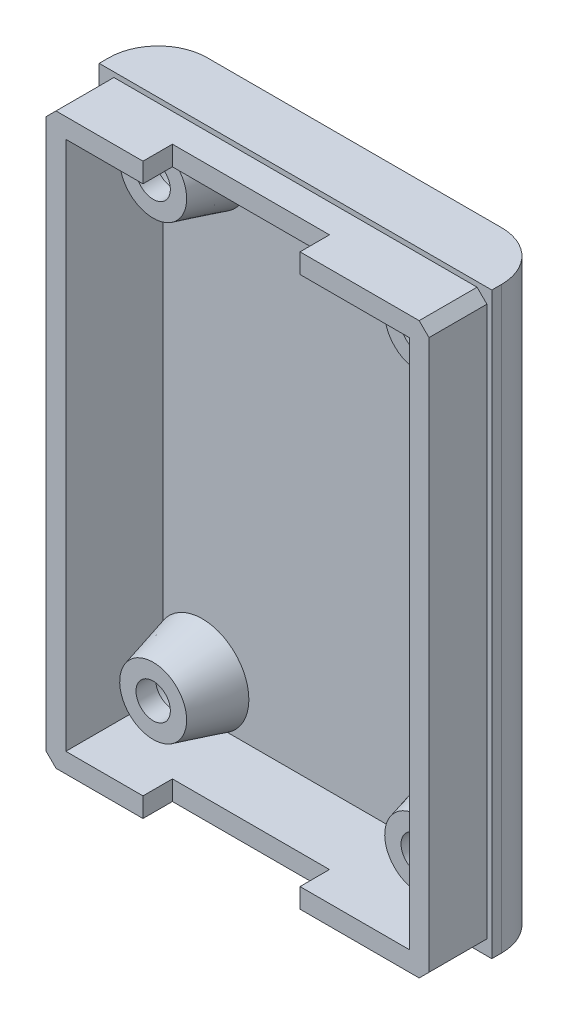
SolidWorks part; units mm, degrees
ref_plane "Спереди" through (0, 0, 0) normal (0, 0, 1) x (1, 0, 0)
ref_plane "Сверху" through (0, 0, 0) normal (0, 1, 0) x (1, 0, 0)
ref_plane "Справа" through (0, 0, 0) normal (1, 0, 0) x (0, 0, -1)
sketch "outline" plane through (0, 0, 0) normal (0, 0, 1) x (1, 0, 0)
  line L0 (-20.5405, -29.5) -> (19.4595, -29.5)
  line L1 (19.4595, -29.5) -> (19.4595, 29.5)
  line L2 (19.4595, 29.5) -> (-20.5405, 29.5)
  line L3 (-20.5405, 29.5) -> (-20.5405, -29.5)
  circle A0 centre (-14.0405, -23) radius 3.25
  circle A1 centre (12.9595, -23) radius 3.25
  circle A2 centre (12.9595, 23) radius 3.25
  circle A3 centre (-14.0405, 23) radius 3.25
  dimension "D1" = 6.5
sketch "base" plane through (0, 0, 0) normal (0, 0, 1) x (1, 0, 0)
  line L0 (-20.5405, -29.5) -> (19.4595, -29.5)
  line L1 (19.4595, -29.5) -> (19.4595, 29.5)
  line L2 (19.4595, 29.5) -> (-20.5405, 29.5)
  line L3 (-20.5405, 29.5) -> (-20.5405, -29.5)
extrude "Бобышка-Вытянуть1" add sketch "base" along normal blind 2
sketch "Эскиз2" plane through (0, 0, 2) normal (0, 0, 1) x (1, 0, 0)
  line L0 (-20.5405, -29.5) -> (19.4595, -29.5) construction
  line L1 (-18.0405, 27) -> (16.9595, 27)
  line L2 (-18.0405, 27) -> (-18.0405, -27)
  line L3 (-18.0405, -27) -> (16.9595, -27)
  line L4 (16.9595, 27) -> (16.9595, -27)
  line L5 (19.4595, -29.5) -> (19.4595, 29.5) construction
  line L6 (19.4595, 29.5) -> (-20.5405, 29.5) construction
  line L7 (-20.5405, 29.5) -> (-20.5405, -29.5) construction
  line L8 (-20.5405, -29.5) -> (19.4595, -29.5)
  line L9 (19.4595, -29.5) -> (19.4595, 29.5)
  line L10 (19.4595, 29.5) -> (-20.5405, 29.5)
  line L11 (-20.5405, 29.5) -> (-20.5405, -29.5)
  dimension "D1" = 2.5
  dimension "D2" = 2.5
  dimension "D3" = 2.5
  dimension "D4" = 2.5
extrude "Бобышка-Вытянуть2" add sketch "Эскиз2" along normal blind 10
sketch "Эскиз3" plane through (0, 0, 2) normal (0, 0, 1) x (1, 0, 0)
  circle A0 centre (-14.0405, -23) radius 3.25 construction
  circle A1 centre (12.9595, -23) radius 3.25 construction
  circle A2 centre (12.9595, 23) radius 3.25 construction
  circle A3 centre (-14.0405, 23) radius 3.25 construction
  circle A4 centre (-14.0405, -23) radius 3.25
  circle A5 centre (12.9595, -23) radius 3.25
  circle A6 centre (12.9595, 23) radius 3.25
  circle A7 centre (-14.0405, 23) radius 3.25
extrude "Бобышка-Вытянуть3" add sketch "Эскиз3" along normal blind 5
sketch "Эскиз4" plane through (0, 0, 0) normal (0, 0, -1) x (-1, 0, 0)
  circle A0 centre (-12.9595, -23) radius 3.25
  circle A1 centre (14.0405, -23) radius 3.25
  circle A2 centre (14.0405, 23) radius 3.25
  circle A3 centre (-12.9595, 23) radius 3.25
  circle A4 centre (-12.9595, -23) radius 2.9
  circle A5 centre (14.0405, -23) radius 2.9
  circle A6 centre (14.0405, 23) radius 2.9
  circle A7 centre (-12.9595, 23) radius 2.9
  dimension "D1" = 5.8
  dimension "D2" = 5.8
  dimension "D3" = 5.8
  dimension "D4" = 5.8
extrude "Вырез-Вытянуть2" cut sketch "Эскиз4" against normal blind 5 contours A5 | A4 | A7 | A6 region at (12.9595, -23, 0) region at (-14.0405, -23, 0) region at (-14.0405, 23, 0) region at (12.9595, 23, 0)
chamfer "Фаска1" distance 1.5 angle 75 4 edges at (-10.7905, 23, 2) (16.2095, 23, 2) (-10.7905, -23, 2) (16.2095, -23, 2) first distance on face at (-10.7905, 23, 2)
sketch "Эскиз6" plane through (0, 0, 0) normal (0, 0, -1) x (-1, 0, 0)
  circle A0 centre (-12.9595, 23) radius 1.75
  circle A1 centre (14.0405, 23) radius 1.75
  circle A2 centre (14.0405, -23) radius 1.75
  circle A3 centre (-12.9595, -23) radius 1.75
  dimension "D1" = 3.5
  dimension "D2" = 3.5
  dimension "D3" = 3.5
  dimension "D4" = 3.5
extrude "Вырез-Вытянуть3" cut sketch "Эскиз6" against normal through all
fillet "Скругление1" radius 5 2 edges at (-20.5405, 0, 0) (19.4595, 0, 0)
sketch "Эскиз7" plane through (0, 0, 12) normal (0, 0, 1) x (1, 0, 0)
  line L0 (-20.5405, -29.5) -> (19.4595, -29.5) construction
  line L1 (18.9595, 29) -> (-20.0405, 29)
  line L2 (18.9595, 29) -> (18.9595, -29)
  line L3 (18.9595, -29) -> (-20.0405, -29)
  line L4 (-20.0405, 29) -> (-20.0405, -29)
  line L5 (19.4595, -29.5) -> (19.4595, 29.5) construction
  line L6 (-20.5405, -29.5) -> (19.4595, -29.5) construction
  line L7 (19.4595, 29.5) -> (-20.5405, 29.5) construction
  line L8 (19.4595, 29.5) -> (-20.5405, 29.5)
  line L9 (-20.5405, -29.5) -> (19.4595, -29.5)
  line L10 (19.4595, -29.5) -> (19.4595, 29.5)
  line L11 (-20.5405, -29.5) -> (19.4595, -29.5)
  line L12 (-20.5405, 29.5) -> (-20.5405, -29.5) construction
  line M8 (-20.5405, 29.5) -> (-20.5405, -29.5)
  line M9 (-20.5405, -29.5) -> (19.4595, -29.5)
  line M10 (19.4595, -29.5) -> (19.4595, 29.5)
  line M11 (19.4595, 29.5) -> (-20.5405, 29.5)
  dimension "D1" = 0.5
  dimension "D2" = 0.5
  dimension "D3" = 0.5
  dimension "D4" = 0.5
extrude "Вырез-Вытянуть6" cut sketch "Эскиз7" against normal blind 6 contours L4 L1 L2 L3 M11 M8 M9 M10 region at (19.3882, 0, 12)
chamfer "Фаска2" distance 1 angle 45 4 edges at (18.9595, 29, 9) (-20.0405, 29, 9) (-20.0405, -29, 9) (18.9595, -29, 9)
sketch "Эскиз8" plane through (0, 0, 12) normal (0, 0, 1) x (1, 0, 0)
  line L1 (20.6044, 35.1619) -> (-22.6889, 35.1619)
  line L2 (20.6044, 35.1619) -> (20.6044, -36.0872)
  line L3 (20.6044, -36.0872) -> (-22.6889, -36.0872)
  line L4 (-22.6889, 35.1619) -> (-22.6889, -36.0872)
extrude "Вырез-Вытянуть7" cut sketch "Эскиз8" against normal blind 0.1
sketch "Эскиз9" plane through (0, 29, 0) normal (0, 1, 0) x (1, 0, 0)
  line L0 (17.9595, -11.9) -> (-19.0405, -11.9) construction
  line L1 (5.8209, -11.9) -> (-10.1791, -11.9)
  line L2 (5.8209, -11.9) -> (5.8209, -8.9)
  line L3 (5.8209, -8.9) -> (-10.1791, -8.9)
  line L4 (-10.1791, -11.9) -> (-10.1791, -8.9)
  line L7 (-2.1791, -11.9) -> (-2.1791, -4.7202) construction
  dimension "D1" = 16
  dimension "D2" = 3
extrude "Вырез-Вытянуть8" cut sketch "Эскиз9" against normal through all
